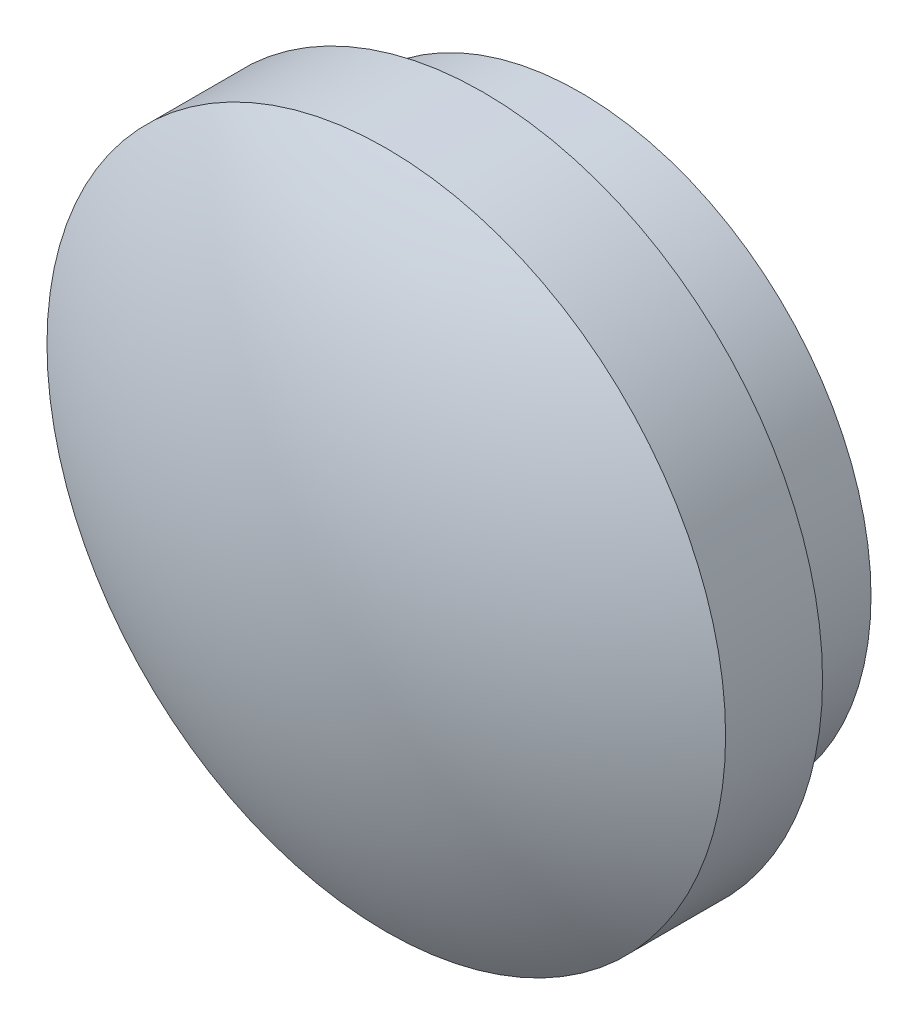
SolidWorks part; units mm, degrees
ref_plane "Front Plane" through (0, 0, 0) normal (0, 0, 1) x (1, 0, 0)
ref_plane "Top Plane" through (0, 0, 0) normal (0, 1, 0) x (1, 0, 0)
ref_plane "Right Plane" through (0, 0, 0) normal (1, 0, 0) x (0, 0, -1)
sketch "Sketch1" plane through (0, 0, 0) normal (0, 0, 1) x (1, 0, 0)
  circle A0 centre (0, 0) radius 7.62
  dimension "D1" = 15.24
extrude "Extrude1" add sketch "Sketch1" along normal blind 2.54
sketch "Sketch2" plane through (0, 0, 2.54) normal (0, 0, 1) x (1, 0, 0)
  circle A0 centre (0, 0) radius 8.89
  dimension "D1" = 17.78
extrude "Extrude2" add sketch "Sketch2" along normal blind 2.54
dome "Dome1" faces to dome 1 distance 2.54 reverse direction no elliptical dome no face at (8.89, 0, 5.08) parameters "D1"=2.54
